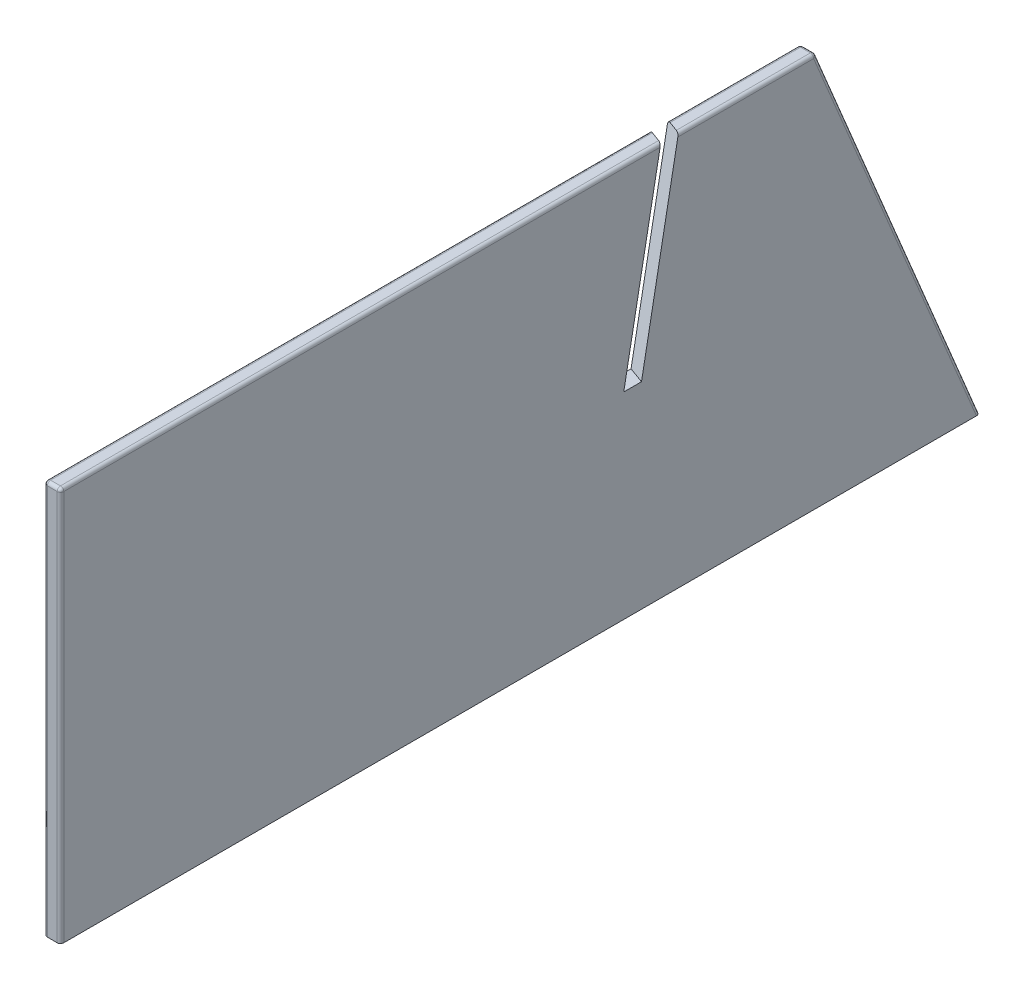
SolidWorks part; units mm, degrees
ref_plane "Front Plane" through (0, 0, 0) normal (0, 0, 1) x (1, 0, 0)
ref_plane "Top Plane" through (0, 0, 0) normal (0, 1, 0) x (1, 0, 0)
ref_plane "Right Plane" through (0, 0, 0) normal (1, 0, 0) x (0, 0, -1)
sketch "Sketch1" plane through (0, 0, 0) normal (1, 0, 0) x (0, 0, -1)
  line L0 (495.3, 304.8) -> (468.4278, 152.4)
  line L1 (0, 0) -> (711.2, 0)
  line L2 (0, 0) -> (0, 304.8)
  line L3 (0, 304.8) -> (711.2, 304.8)
  line L4 (711.2, 0) -> (711.2, 304.8)
  line L5 (468.4278, 152.4) -> (455.5319, 152.4)
  line L6 (455.5319, 152.4) -> (482.4041, 304.8)
  line L7 (482.4041, 304.8) -> (495.3, 304.8)
  line L8 (455.5319, 152.4) -> (455.5319, 304.8) construction
  line L9 (711.2, 0) -> (584.2, 304.8)
  line L10 (584.2, 304.8) -> (711.2, 304.8)
  line L11 (711.2, 0) -> (711.2, 304.8)
  dimension "D1" = 711.2
  dimension "D2" = 304.8
  dimension "D3" = 152.4
  dimension "D4" = 10
  dimension "D5" = 12.7
  dimension "D6" = 215.9
  dimension "D7" = 127
extrude "Boss-Extrude2" add sketch "Sketch1" along normal blind 12.7 contours L8 L1 L9 L3 L0 L5 | L1 L8 L3 L2 | L8 L6 L3 | L7 L0 L5 L6 region at (0, 145.4663, -321.8799) region at (0, 254, -464.4893)
ref_axis "Axis1" through (0, 0, 0) along (0, 1, 0)
ref_plane "Plane1" through (11.2144, 0, 4.0817) normal (0.9397, 0, 0.342) x (0, 1, 0)
sketch "Sketch3" plane through (11.2144, 0, 4.0817) normal (0.9397, 0, 0.342) x (0, 1, 0)
  line L0 (304.8, -453.4957) -> (152.4, -426.6234)
  line L1 (152.4, -426.6234) -> (152.4, -413.7275)
  line L2 (152.4, -413.7275) -> (304.8, -440.5997)
  line L3 (304.8, -440.5997) -> (304.8, -453.4957)
  line L4 (304.8, 0) -> (304.8, -548.9684) construction
  line L5 (0, 0) -> (304.8, 0) construction
  point P2 (228.6, -427.1636)
  point P5 (152.4, -420.1755)
  dimension "D1" = 12.7
  dimension "D2" = 152.4
  dimension "D3" = 0
  dimension "D4" = 453.4957
  dimension "D5" = 10
extrude "Cut-Extrude1" cut sketch "Sketch3" against normal through all contours L2 L3 L0 L1
fillet "Fillet1" radius 2.54 10 edges at (6.35, 304.8, -584.2) (12.7, 304.8, -531.0888) (0, 304.8, -533.4) (12.7, 152.4, -647.7) (0, 152.4, -647.7) (0, 152.4, 0) (12.7, 152.4, 0) (6.35, 304.8, 0) (12.7, 304.8, -232.127) (0, 304.8, -234.4382)
